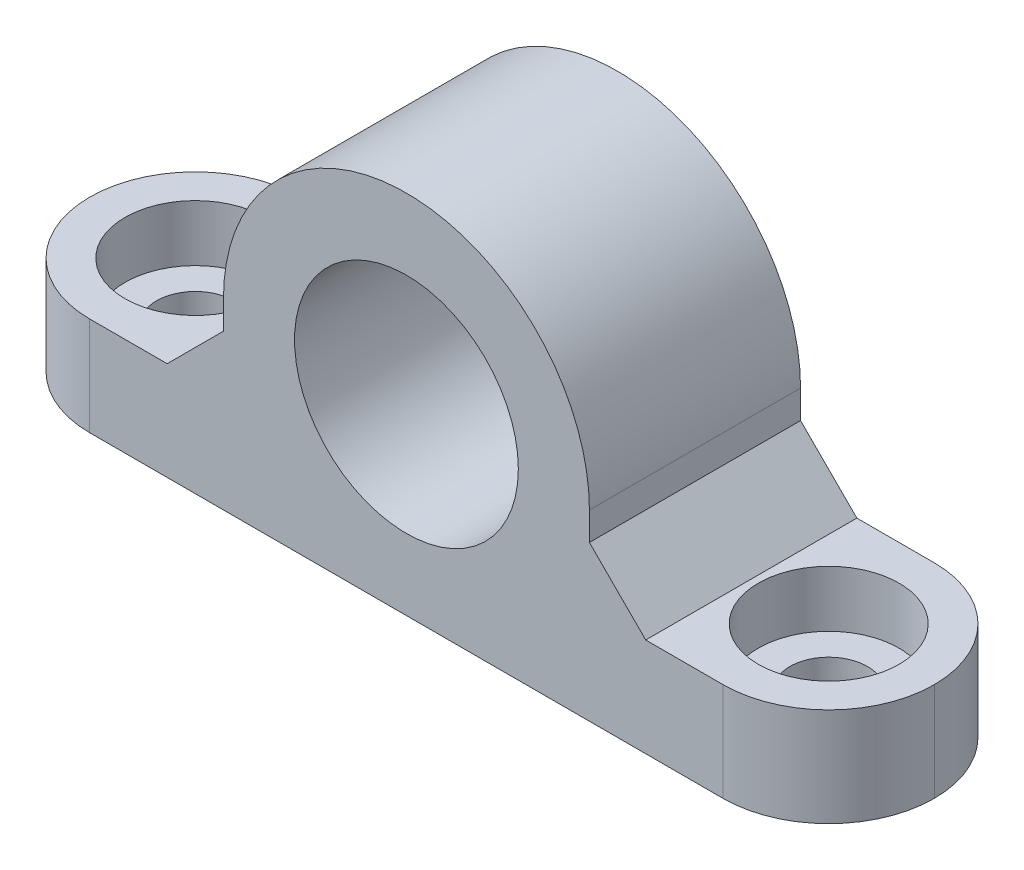
SolidWorks part; units mm, degrees
material "ABS"
ref_plane "Front Plane" through (0, 0, 0) normal (0, 0, 1) x (1, 0, 0)
ref_plane "Top Plane" through (0, 0, 0) normal (0, 1, 0) x (1, 0, 0)
ref_plane "Right Plane" through (0, 0, 0) normal (1, 0, 0) x (0, 0, -1)
sketch "Sketch1" plane through (0, 0, 0) normal (0, 1, 0) x (1, 0, 0)
  line L1 (-30, 7.5) -> (30, 7.5)
  line L2 (-30, 7.5) -> (-30, -7.5)
  line L3 (-30, -7.5) -> (30, -7.5)
  line L4 (30, 7.5) -> (30, -7.5)
  line L5 (-30, 7.5) -> (30, -7.5) construction
  line L6 (-30, -7.5) -> (30, 7.5) construction
  point P0 (0, 0)
  dimension "D1" = 15
  dimension "D2" = 60
extrude "Boss-Extrude1" add sketch "Sketch1" along normal blind 7
sketch "Sketch4" plane through (0, 0, 7.5) normal (0, 0, 1) x (1, 0, 0)
  line L0 (-30, 7) -> (30, 7) construction
  line L1 (-13, 13) -> (13, 13) construction
  line L2 (-13, 13) -> (-13, 7) construction
  line L3 (-13, 13) -> (-13, 7)
  line L4 (13, 13) -> (13, 7) construction
  line L5 (-13, 13) -> (13, 7) construction
  line L6 (-13, 7) -> (13, 13) construction
  line L7 (-30, 0) -> (30, 0) construction
  line L8 (-13, 7) -> (13, 7)
  line L9 (13, 7) -> (13, 13)
  arc A0 (-13, 13) -> (13, 13) centre (0, 13) cw
  point P0 (0, 10)
  point P9 (0, 0)
  dimension "D2" = 13
  dimension "D1" = 13
extrude "Boss-Extrude2" add sketch "Sketch4" against normal up to surface (15 mm away) up to face at (0, 3.5, -7.5)
chamfer "Chamfer1" distance 4 angle 45 2 edges
sketch "Sketch2" plane through (0, 7, 0) normal (0, 1, 0) x (1, 0, 0)
  line L0 (0, 0) -> (0, 16.1547) construction
  line L1 (30, 7.5) -> (17, 7.5) construction
  line L2 (-30, 7.5) -> (-30, -7.5) construction
  circle A0 centre (-22.5, 0) radius 2.75
  circle A1 centre (22.5, 0) radius 2.75
  dimension "D3" = 5.5
  dimension "D1" = 7.5
  dimension "D2" = 7.5
extrude "Cut-Extrude1" cut sketch "Sketch2" against normal through all
sketch "Sketch3" plane through (0, 7, 0) normal (0, 1, 0) x (1, 0, 0)
  line L0 (0, 0) -> (0, 12.9854) construction
  circle A0 centre (-22.5, 0) radius 5
  circle A1 centre (22.5, 0) radius 5
  dimension "D1" = 10
extrude "Cut-Extrude2" cut sketch "Sketch3" against normal offset from surface 3 and the other way through all up to face at (22.5, 0, -2.75)
sketch "Sketch5" plane through (0, 0, 7.5) normal (0, 0, 1) x (1, 0, 0)
  circle A0 centre (0, 13) radius 7.95
  circle A2 centre (0, 13) radius 7.95 construction
  arc A3 (13, 13) -> (-13, 13) centre (0, 13) ccw construction
extrude "Cut-Extrude3" cut sketch "Sketch5" against normal through all
fillet "Fillet2" radius 7.5 4 edges at (30, 3.5, 7.5) (30, 3.5, -7.5) (-30, 3.5, -7.5) (-30, 3.5, 7.5)
equation "\"D2@Sketch2\" = \"D1@Sketch2\""
equation "\"D1@Sketch4\" = \"D2@Sketch4\""
